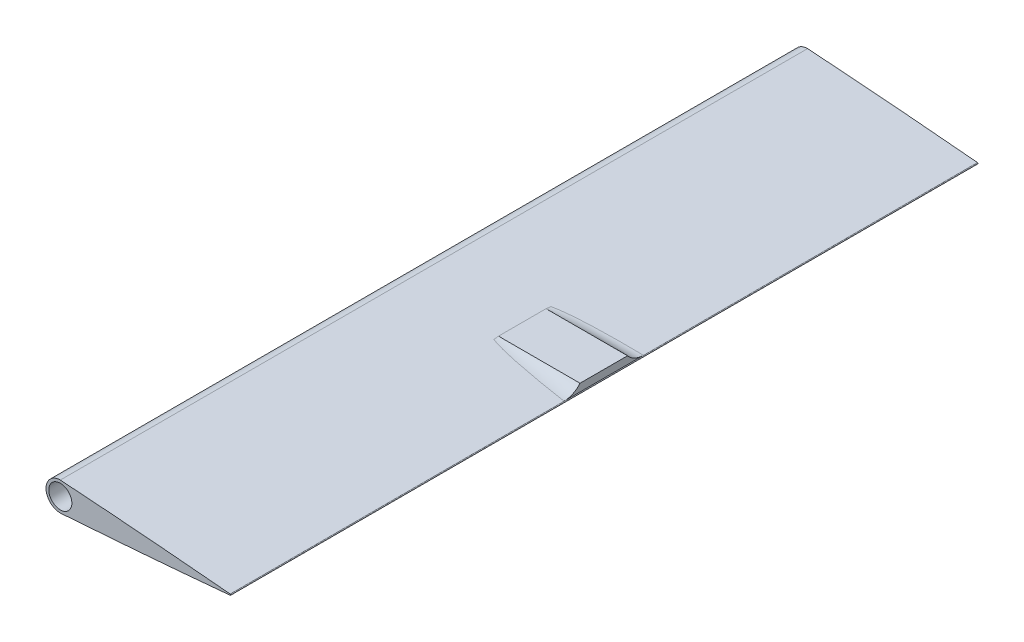
SolidWorks part; units mm, degrees
material "Manual Density from Real Component Timone Legno"
ref_plane "Piano frontale" through (0, 0, 0) normal (0, 0, 1) x (1, 0, 0)
ref_plane "Piano superiore" through (0, 0, 0) normal (0, 1, 0) x (1, 0, 0)
ref_plane "Piano destro" through (0, 0, 0) normal (1, 0, 0) x (0, 0, -1)
other "Centro di massa"
curve "Curva1"
  spline degree 3 poles (100, 0.084, 0) (98.3335, 0.2367, 0) (95.0012, 0.5422, 0) (88.3356, 1.1109, 0) (80.0033, 1.7636, 0) (70.003, 2.4579, 0) (60.0031, 3.0617, 0) (50.003, 3.5521, 0) (40.0026, 3.9029, 0) (31.667, 4.0253, 0) (24.9992, 3.9769, 0) (19.9978, 3.845, 0) (14.9934, 3.5925, 0) (10.8272, 3.2377, 0) (7.4891, 2.814, 0) (4.9936, 2.4037, 0) (2.8496, 1.8679, 0) (1.1654, 1.321, 0) (-0.6646, 0, 0) (1.1654, -1.321, 0) (2.8496, -1.8679, 0) (4.9936, -2.4037, 0) (7.4891, -2.814, 0) (10.8272, -3.2377, 0) (14.9934, -3.5925, 0) (19.9978, -3.845, 0) (24.9992, -3.9769, 0) (31.667, -4.0253, 0) (40.0026, -3.9029, 0) (50.003, -3.5521, 0) (60.0031, -3.0617, 0) (70.003, -2.4579, 0) (80.0033, -1.7636, 0) (88.3356, -1.1109, 0) (95.0012, -0.5422, 0) (98.3335, -0.2367, 0) (100, -0.084, 0) knots 0 0 0 0 0.024876 0.049742 0.099443 0.149112 0.198751 0.248359 0.297937 0.347491 0.372267 0.397051 0.421859 0.446731 0.45922 0.471791 0.48456 0.491195 0.5 0.508805 0.51544 0.528209 0.54078 0.553269 0.578141 0.602949 0.627733 0.652509 0.702063 0.751641 0.801249 0.850888 0.900557 0.950258 0.975124 1 1 1 1
sketch "Schizzo2" plane through (0, 0, 0) normal (0, 0, 1) x (1, 0, 0)
  line L0 (75, 2.1072) -> (75, -2.1072) construction
  arc A0 (100, 0.084) -> (100, -0.084) centre (100, 0) cw
  arc A1 (75, 2.1072) -> (75, -2.1072) centre (75, 0) ccw
  spline S1 degree 3 poles (100, 0.084) (98.3335, 0.2367) (95.0012, 0.5422) (88.3356, 1.1109) (81.6686, 1.6332) (76.6669, 1.9915) (75, 2.1072) knots 0 0 0 0 0.024876 0.049742 0.099443 0.124282 0.124282 0.124282 0.124282
  spline S2 degree 3 poles (75, -2.1072) (76.6669, -1.9915) (81.6686, -1.6332) (88.3356, -1.1109) (95.0012, -0.5422) (98.3335, -0.2367) (100, -0.084) knots 0.875718 0.875718 0.875718 0.875718 0.900557 0.950258 0.975124 1 1 1 1
  spline S3 degree 3 poles (1265.2106, 6875.158) (458.4991, -96.3936) (277.9953, -15.0713) (88.3356, 1.1109) (80.0033, 1.7636) (70.003, 2.4579) (60.0031, 3.0617) (50.003, 3.5521) (40.0026, 3.9029) (31.667, 4.0253) (24.9992, 3.9769) (19.9978, 3.845) (14.9934, 3.5925) (10.8272, 3.2377) (7.4891, 2.814) (4.9936, 2.4037) (2.8496, 1.8679) (1.1654, 1.321) (-0.6646, 0) (1.1654, -1.321) (2.8496, -1.8679) (4.9936, -2.4037) (7.4891, -2.814) (10.8272, -3.2377) (14.9934, -3.5925) (19.9978, -3.845) (24.9992, -3.9769) (31.667, -4.0253) (40.0026, -3.9029) (50.003, -3.5521) (60.0031, -3.0617) (70.003, -2.4579) (80.0033, -1.7636) (88.3356, -1.1109) (277.9935, 15.0711) (458.4956, 96.392) (1265.1864, -6874.9491) knots -2.730056 -2.730056 -2.730056 -2.730056 0.024876 0.049742 0.099443 0.149112 0.198751 0.248359 0.297937 0.347491 0.372267 0.397051 0.421859 0.446731 0.45922 0.471791 0.48456 0.491195 0.5 0.508805 0.51544 0.528209 0.54078 0.553269 0.578141 0.602949 0.627733 0.652509 0.702063 0.751641 0.801249 0.850888 0.900557 0.950258 0.975124 3.730029 3.730029 3.730029 3.730029 only from (100, 0.084) to (100, -0.084) construction
  spline S4 degree 3 poles (100, 0.084) (98.3335, 0.2367) (95.0012, 0.5422) (88.3356, 1.1109) (80.0033, 1.7636) (70.003, 2.4579) (60.0031, 3.0617) (50.003, 3.5521) (40.0026, 3.9029) (31.667, 4.0253) (24.9992, 3.9769) (19.9978, 3.845) (14.9934, 3.5925) (10.8272, 3.2377) (7.4891, 2.814) (4.9936, 2.4037) (2.8496, 1.8679) (1.1654, 1.321) (-0.6646, 0) (1.1654, -1.321) (2.8496, -1.8679) (4.9936, -2.4037) (7.4891, -2.814) (10.8272, -3.2377) (14.9934, -3.5925) (19.9978, -3.845) (24.9992, -3.9769) (31.667, -4.0253) (40.0026, -3.9029) (50.003, -3.5521) (60.0031, -3.0617) (70.003, -2.4579) (80.0033, -1.7636) (88.3356, -1.1109) (95.0012, -0.5422) (98.3335, -0.2367) (100, -0.084) knots 0 0 0 0 0.024876 0.049742 0.099443 0.149112 0.198751 0.248359 0.297937 0.347491 0.372267 0.397051 0.421859 0.446731 0.45922 0.471791 0.48456 0.491195 0.5 0.508805 0.51544 0.528209 0.54078 0.553269 0.578141 0.602949 0.627733 0.652509 0.702063 0.751641 0.801249 0.850888 0.900557 0.950258 0.975124 1 1 1 1 construction
  dimension "D3" = 0.084
  dimension "D1" = 25
  dimension "D2" = 4.2144
extrude "CorpoTimone" add sketch "Schizzo2" along normal blind 110 contours A1 S2 A0 S1 region at (82.7685, 0, 0)
sketch "Schizzo3" plane through (0, 0, 110) normal (0, 0, 1) x (1, 0, 0)
  circle A0 centre (75, 0) radius 1.7
  dimension "D1" = 3.4
extrude "ForoPerno" cut sketch "Schizzo3" against normal through all
sketch "Schizzo4" plane through (0, 0, 0) normal (0, 1, 0) x (1, 0, 0)
  line L0 (88, -55) -> (75, -55) construction
  line L1 (100, -51.5) -> (88, -51.5)
  line L2 (100, -51.5) -> (100, -58.5)
  line L3 (100, -58.5) -> (88, -58.5)
  line L4 (88, -51.5) -> (88, -58.5)
  line L5 (75, -110) -> (75, 0) construction
  line L6 (100, -110) -> (100, 0) construction
  dimension "D1" = 12
  dimension "D2" = 7
extrude "SupportoCollegamentoServomotore" add sketch "Schizzo4" along normal blind 1.2
fillet "RaccordoSupporto" radius 3 2 edges
ref_plane "Piano1" through (75, 0, 0) normal (1, 0, 0) x (0, 0, -1)
ref_plane "Piano2" through (0, 0, 55) normal (0, 0, 1) x (1, 0, 0)
ref_axis "Assi1" through (75, -0.65, 55) along (0, 1, 0)
ref_point "Punto1"
